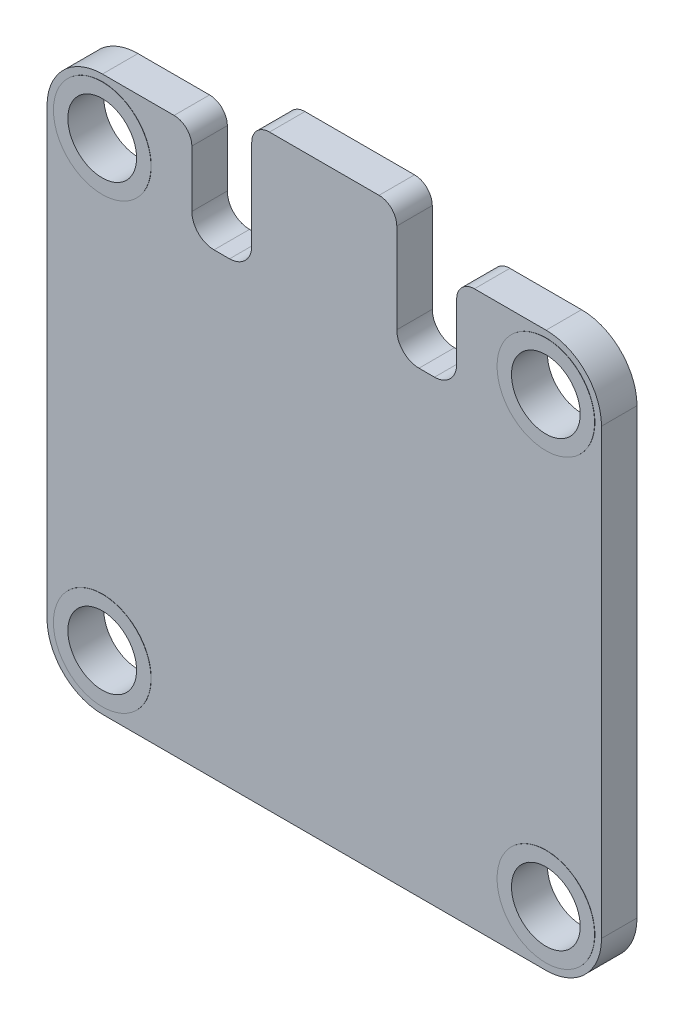
SolidWorks part; units mm, degrees
note: '?' marks a value the reader was unsure of.
ref_plane "Front Plane" through (0, 0, 0) normal (0, 0, 1) x (1, 0, 0)
ref_plane "Top Plane" through (0, 0, 0) normal (0, 1, 0) x (1, 0, 0)
ref_plane "Right Plane" through (0, 0, 0) normal (1, 0, 0) x (0, 0, -1)
sketch "Sketch2" plane through (0, 0, 0) normal (0, 0, 1) x (1, 0, 0)
  line L1 (-12.5, 12.5) -> (12.5, 12.5)
  line L2 (-12.5, 12.5) -> (-12.5, -12.5)
  line L3 (-12.5, -12.5) -> (12.5, -12.5)
  line L4 (12.5, 12.5) -> (12.5, -12.5)
  line L5 (-12.5, 12.5) -> (12.5, -12.5) construction
  line L6 (-12.5, -12.5) -> (12.5, 12.5) construction
  point P0 (0, 0)
  dimension "D1" = 25
  dimension "D2" = 25
extrude "Boss-Extrude1 (module PCB)" add sketch "Sketch2" along normal blind 1.6
fillet "Fillet1 (corners)" radius 2.5 4 edges at (-12.5, -12.5, 0.8) (12.5, -12.5, 0.8) (12.5, 12.5, 0.8) (-12.5, 12.5, 0.8)
sketch "Sketch3" plane through (0, 0, 0) normal (0, 0, 1) x (1, 0, 0)
  line L2 (12.5, -10) -> (12.5, 10) construction
  circle A0 centre (10, 10) radius 1.55
  dimension "D2" = 3.1
  dimension "D1" = 2.5
  dimension "D3" = 2.5
extrude "Cut-Extrude1 (first MH)" cut sketch "Sketch3" along normal up to next
sketch "Sketch4" plane through (0, 0, 0) normal (0, 0, 1) x (1, 0, 0)
  circle A0 centre (10, 10) radius 1.55 construction
  circle A1 centre (10, 10) radius 1.55
  circle A2 centre (10, 10) radius 2.2
  circle A3 centre (10, 10) radius 2.2
  dimension "D1" = 0.65
extrude "Boss-Extrude2 (PTH for first MH)" add sketch "Sketch4" against normal blind 0.01
sketch "Sketch7 (keepout for first MH)" plane through (0, 0, 0) normal (0, 0, 1) x (1, 0, 0)
  circle A0 centre (10, 10) radius 3.5
  dimension "D1" = 7
sketch "Sketch8 (keepout for board outline)" plane through (0, 0, 0) normal (0, 0, 1) x (1, 0, 0)
  line L9 (-10.6, 10) -> (-10.6, -10)
  line L10 (-10, -10.6) -> (10, -10.6)
  line L11 (10.6, -10) -> (10.6, 10)
  line L12 (10, 10.6) -> (-10, 10.6)
  line L13 (-10.6, 10) -> (-10.6, -10)
  line L14 (-10, -10.6) -> (10, -10.6)
  line L15 (10.6, -10) -> (10.6, 10)
  line L16 (10, 10.6) -> (-10, 10.6)
  arc A8 (-10, 10.6) -> (-10.6, 10) centre (-10, 10) ccw
  arc A9 (-10.6, -10) -> (-10, -10.6) centre (-10, -10) ccw
  arc A10 (10, -10.6) -> (10.6, -10) centre (10, -10) ccw
  arc A11 (10.6, 10) -> (10, 10.6) centre (10, 10) ccw
  arc A12 (-10, 10.6) -> (-10.6, 10) centre (-10, 10) ccw
  arc A13 (-10.6, -10) -> (-10, -10.6) centre (-10, -10) ccw
  arc A14 (10, -10.6) -> (10.6, -10) centre (10, -10) ccw
  arc A15 (10.3087, 9.4855) -> (10, 10.6) centre (10, 10) ccw
  dimension "D1" = 1.9
ref_plane "Plane1 (module midplane)" through (0, 0, 0.8) normal (0, 0, 1) x (1, 0, 0)
mirror "Mirror1 (PTH for first MH)" about plane through (0, 0, 0.8) normal (0, 0, 1) of "Boss-Extrude2 (PTH for first MH)"
ref_axis "Axis1 (module centre)" through (0, 0, -0.091) along (0, 0, 1)?
mirror "Mirror2 (second MH & PTH)" about plane through (0, 0, 0) normal (1, 0, 0) of "Cut-Extrude1 (first MH)", "Mirror1 (PTH for first MH)", "Boss-Extrude2 (PTH for first MH)"
mirror "Mirror3 (remaining MH & PTH)" about plane through (0, 0, 0) normal (0, 1, 0) of "Mirror2 (second MH & PTH)", "Cut-Extrude1 (first MH)", "Boss-Extrude2 (PTH for first MH)", "Mirror1 (PTH for first MH)"
sketch "Sketch7" plane through (0, 0, -0.01) normal (0, 0, -1) x (-1, 0, 0)
  line L0 (-10, -7.8) -> (-12.2, -7.8)
  line L1 (-12.2, -7.8) -> (-12.2, -10)
  line L2 (-10, -12.2) -> (-7.8, -12.2)
  line L3 (-7.8, -12.2) -> (-7.8, -10)
  circle A0 centre (-10, -10) radius 2.2 construction
  arc A1 (-10, -7.8) -> (-12.2, -10) centre (-10, -10) ccw
  arc A2 (-10, -12.2) -> (-7.8, -10) centre (-10, -10) ccw
extrude "Boss-Extrude1" add sketch "Sketch7" against normal up to next
sketch "Sketch5" plane through (0, 12.5, 0) normal (0, 1, 0) x (1, 0, 0)
  line L0 (10, 0) -> (-10, 0) construction
  line L1 (3.27, 0) -> (-3.27, 0)
  line L2 (3.27, 0) -> (3.27, -1.6)
  line L3 (3.27, -1.6) -> (-3.27, -1.6)
  line L4 (-3.27, 0) -> (-3.27, -1.6)
  line L5 (10, -1.6) -> (-10, -1.6) construction
  line L6 (0, 2.9926) -> (0, -3.8865) construction
  line L9 (0, 0.091) -> (0, -1.691) construction
  dimension "D1" = 6.54
extrude "Boss-Extrude3 (tip of edge connector)" add sketch "Sketch5" along normal blind 1.5
sketch "Sketch6" plane through (0, 12.5, 0) normal (0, 1, 0) x (1, 0, 0)
  line L0 (-3.27, 0) -> (-10, 0) construction
  line L1 (-3.27, -1.6) -> (-5.97, -1.6)
  line L2 (-3.27, -1.6) -> (-3.27, 0)
  line L3 (-3.27, 0) -> (-5.97, 0)
  line L4 (-5.97, -1.6) -> (-5.97, 0)
  line L6 (3.27, -1.6) -> (5.97, -1.6)
  line L7 (3.27, -1.6) -> (3.27, 0)
  line L8 (3.27, 0) -> (5.97, 0)
  line L9 (5.97, -1.6) -> (5.97, 0)
  dimension "D1" = 2.7
  dimension "D2" = 2.7
extrude "Cut-Extrude2 (sides of edge connector)" cut sketch "Sketch6" against normal blind 4.35
fillet "Fillet2 (tip of edge connector)" radius 0.8 2 edges at (3.27, 14, 0.8) (-3.27, 14, 0.8)
fillet "Fillet3 (base of edge connector)" radius 1 4 edges at (-5.97, 8.15, 0.8) (-3.27, 8.15, 0.8) (5.97, 8.15, 0.8) (3.27, 8.15, 0.8)
fillet "Fillet4 (adjacent to edge connector)" radius 0.8 2 edges at (-5.97, 12.5, 0.8) (5.97, 12.5, 0.8)
equation "\"D\"=3.5"
equation "\"E\"=2.7"
equation "\"D2@Sketch6\"=\"E\""
equation "\"D1@Sketch6\"=\"E\""
